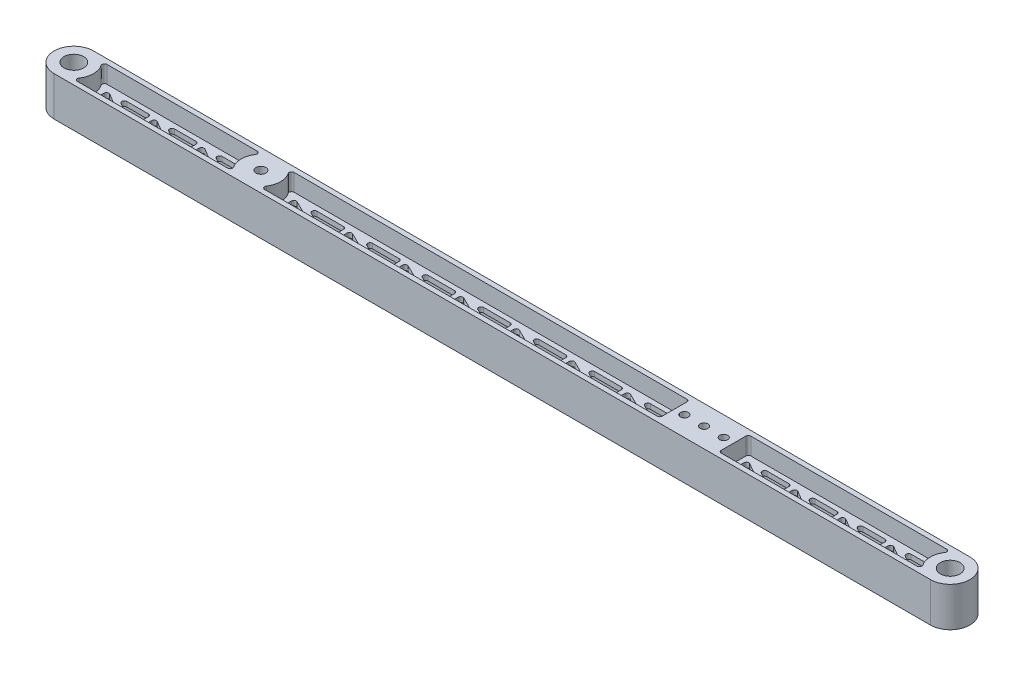
SolidWorks part; units mm, degrees
ref_plane "Front Plane" through (0, 0, 0) normal (0, 0, 1) x (1, 0, 0)
ref_plane "Top Plane" through (0, 0, 0) normal (0, 1, 0) x (1, 0, 0)
ref_plane "Right Plane" through (0, 0, 0) normal (1, 0, 0) x (0, 0, -1)
sketch "Sketch2" plane through (0, 0, 0) normal (0, 1, 0) x (1, 0, 0)
  line L0 (0, 0) -> (120.65, 0)
  line L1 (0, 0) -> (565.15, 0)
  line L2 (0, 0) -> (0, 25.4) construction
  line L3 (0, 25.4) -> (565.15, 25.4)
  line L4 (565.15, 0) -> (565.15, 25.4) construction
  line L5 (120.65, 0) -> (120.65, 25.4) construction
  circle A0 centre (120.65, 12.7) radius 12.7
  arc A1 (565.15, 25.4) -> (565.15, 0) centre (565.15, 12.7) cw
  circle A2 centre (120.65, 12.7) radius 3.175
  circle A3 centre (565.15, 12.7) radius 6.35
  arc A4 (0, 25.4) -> (0, 0) centre (0, 12.7) ccw
  circle A5 centre (0, 12.7) radius 6.35
  dimension "D4" = 6.35
  dimension "D5" = 12.7
  dimension "D6" = 12.7
  dimension "D1" = 565.15
  dimension "D2" = 25.4
  dimension "D3" = 120.65
extrude "Boss-Extrude1" add sketch "Sketch2" along normal blind 25.4 contours A0 L3 L2 L0 | A0 A2 | A1 L3 A0 L1 A3 region at (52.5215, 0, -12.7) region at (350.4658, 0, -12.7) region at (108.3092, 0, -12.7)
sketch "Sketch12" plane through (0, 0, -25.4) normal (0, 0, -1) x (-1, 0, 0)
  line L0 (-565.15, 25.4) -> (-425.45, 25.4)
  line L1 (0, 25.4) -> (-565.15, 25.4) construction
  line L2 (-387.35, 0) -> (-425.45, 0)
  line L3 (-425.45, 25.4) -> (-425.45, 0)
  line L5 (-387.35, 0) -> (-387.35, 25.4)
  line L6 (-425.45, 25.4) -> (-387.35, 25.4)
  line L7 (0, 0) -> (-565.15, 0) construction
  dimension "D1" = 139.7
  dimension "D2" = 38.1
sketch "Sketch13" plane through (0, 25.4, 0) normal (0, 1, 0) x (1, 0, 0)
  line L0 (565.15, 25.4) -> (565.15, 0) construction
  line L1 (0, 25.4) -> (0, 0) construction
  line L2 (565.15, 25.4) -> (565.15, 0) construction
  line L3 (565.15, 22.225) -> (0, 22.225)
  line L4 (0, 3.175) -> (565.15, 3.175)
  line L5 (565.15, 25.4) -> (425.45, 25.4) construction
  line L6 (0, 0) -> (565.15, 0) construction
  line L7 (12.7, 12.7) -> (15.875, 12.7) construction
  line L8 (15.875, 19.05) -> (15.875, 6.35)
  line L9 (15.875, 6.35) -> (37.189, 6.35)
  line L10 (37.189, 6.35) -> (15.875, 19.05)
  line L11 (22.0777, 19.05) -> (43.3917, 6.35)
  line L12 (43.3917, 6.35) -> (43.3917, 19.05)
  line L13 (43.3917, 19.05) -> (22.0777, 19.05)
  line L14 (46.5667, 19.05) -> (46.5667, 6.35)
  line L15 (46.5667, 6.35) -> (67.8806, 6.35)
  line L16 (67.8806, 6.35) -> (46.5667, 19.05)
  line L17 (52.7694, 19.05) -> (74.0833, 6.35)
  line L18 (74.0833, 6.35) -> (74.0833, 19.05)
  line L19 (74.0833, 19.05) -> (52.7694, 19.05)
  line L20 (43.3917, 12.7) -> (46.5667, 12.7) construction
  line L21 (77.2583, 19.05) -> (77.2583, 6.35)
  line L22 (77.2583, 6.35) -> (98.5723, 6.35)
  line L23 (98.5723, 6.35) -> (77.2583, 19.05)
  line L24 (83.461, 19.05) -> (104.775, 6.35)
  line L25 (104.775, 6.35) -> (104.775, 19.05)
  line L26 (104.775, 19.05) -> (83.461, 19.05)
  line L27 (74.0833, 12.7) -> (77.2583, 12.7) construction
  line L28 (107.95, 12.7) -> (104.775, 12.7) construction
  line L29 (133.35, 12.7) -> (136.525, 12.7) construction
  line L30 (136.525, 19.05) -> (136.525, 6.35)
  line L31 (136.525, 6.35) -> (162.0538, 6.35)
  line L32 (162.0538, 6.35) -> (136.525, 19.05)
  line L33 (143.6533, 19.05) -> (169.1821, 6.35)
  line L34 (169.1821, 6.35) -> (169.1821, 19.05)
  line L35 (169.1821, 19.05) -> (143.6533, 19.05)
  line L36 (387.35, 25.4) -> (387.35, 0)
  line L37 (425.45, 25.4) -> (387.35, 25.4) construction
  line L38 (387.35, 0) -> (425.45, 0)
  line L39 (425.45, 0) -> (425.45, 25.4)
  line L40 (387.35, 25.4) -> (425.45, 25.4) construction
  line L41 (425.45, 25.4) -> (387.35, 25.4)
  line L42 (172.3571, 19.05) -> (172.3571, 6.35)
  line L43 (172.3571, 6.35) -> (197.886, 6.35)
  line L44 (197.886, 6.35) -> (172.3571, 19.05)
  line L45 (179.4855, 19.05) -> (205.0143, 6.35)
  line L46 (205.0143, 6.35) -> (205.0143, 19.05)
  line L47 (205.0143, 19.05) -> (179.4855, 19.05)
  line L48 (169.1821, 12.7) -> (172.3571, 12.7) construction
  line L49 (208.1893, 19.05) -> (208.1893, 6.35)
  line L50 (208.1893, 6.35) -> (233.7181, 6.35)
  line L51 (233.7181, 6.35) -> (208.1893, 19.05)
  line L52 (215.3176, 19.05) -> (240.8464, 6.35)
  line L53 (240.8464, 6.35) -> (240.8464, 19.05)
  line L54 (240.8464, 19.05) -> (215.3176, 19.05)
  line L55 (205.0143, 12.7) -> (208.1893, 12.7) construction
  line L56 (244.0214, 19.05) -> (244.0214, 6.35)
  line L57 (244.0214, 6.35) -> (269.5502, 6.35)
  line L58 (269.5502, 6.35) -> (244.0214, 19.05)
  line L59 (251.1498, 19.05) -> (276.6786, 6.35)
  line L60 (276.6786, 6.35) -> (276.6786, 19.05)
  line L61 (276.6786, 19.05) -> (251.1498, 19.05)
  line L62 (240.8464, 12.7) -> (244.0214, 12.7) construction
  line L63 (279.8536, 19.05) -> (279.8536, 6.35)
  line L64 (279.8536, 6.35) -> (305.3824, 6.35)
  line L65 (305.3824, 6.35) -> (279.8536, 19.05)
  line L66 (286.9819, 19.05) -> (312.5107, 6.35)
  line L67 (312.5107, 6.35) -> (312.5107, 19.05)
  line L68 (312.5107, 19.05) -> (286.9819, 19.05)
  line L69 (276.6786, 12.7) -> (279.8536, 12.7) construction
  line L70 (315.6857, 19.05) -> (315.6857, 6.35)
  line L71 (315.6857, 6.35) -> (341.2145, 6.35)
  line L72 (341.2145, 6.35) -> (315.6857, 19.05)
  line L73 (322.814, 19.05) -> (348.3429, 6.35)
  line L74 (348.3429, 6.35) -> (348.3429, 19.05)
  line L75 (348.3429, 19.05) -> (322.814, 19.05)
  line L76 (312.5107, 12.7) -> (315.6857, 12.7) construction
  line L77 (351.5179, 19.05) -> (351.5179, 6.35)
  line L78 (351.5179, 6.35) -> (377.0467, 6.35)
  line L79 (377.0467, 6.35) -> (351.5179, 19.05)
  line L80 (358.6462, 19.05) -> (384.175, 6.35)
  line L81 (384.175, 6.35) -> (384.175, 19.05)
  line L82 (384.175, 19.05) -> (358.6462, 19.05)
  line L83 (348.3429, 12.7) -> (351.5179, 12.7) construction
  line L84 (425.45, 12.7) -> (428.625, 12.7) construction
  line L85 (428.625, 19.05) -> (428.625, 6.35)
  line L86 (428.625, 6.35) -> (450.1567, 6.35)
  line L87 (450.1567, 6.35) -> (428.625, 19.05)
  line L88 (434.8745, 19.05) -> (456.4062, 6.35)
  line L89 (456.4062, 6.35) -> (456.4062, 19.05)
  line L90 (456.4062, 19.05) -> (434.8745, 19.05)
  line L91 (459.5812, 19.05) -> (459.5812, 6.35)
  line L92 (459.5812, 6.35) -> (481.113, 6.35)
  line L93 (481.113, 6.35) -> (459.5812, 19.05)
  line L94 (465.8308, 19.05) -> (487.3625, 6.35)
  line L95 (487.3625, 6.35) -> (487.3625, 19.05)
  line L96 (487.3625, 19.05) -> (465.8308, 19.05)
  line L97 (456.4062, 12.7) -> (459.5812, 12.7) construction
  line L98 (490.5375, 19.05) -> (490.5375, 6.35)
  line L99 (490.5375, 6.35) -> (512.0692, 6.35)
  line L100 (512.0692, 6.35) -> (490.5375, 19.05)
  line L101 (496.787, 19.05) -> (518.3187, 6.35)
  line L102 (518.3187, 6.35) -> (518.3187, 19.05)
  line L103 (518.3187, 19.05) -> (496.787, 19.05)
  line L104 (487.3625, 12.7) -> (490.5375, 12.7) construction
  line L105 (521.4937, 19.05) -> (521.4937, 6.35)
  line L106 (521.4937, 6.35) -> (543.0255, 6.35)
  line L107 (543.0255, 6.35) -> (521.4937, 19.05)
  line L108 (527.7433, 19.05) -> (549.275, 6.35)
  line L109 (549.275, 6.35) -> (549.275, 19.05)
  line L110 (549.275, 19.05) -> (527.7433, 19.05)
  line L111 (518.3187, 12.7) -> (521.4937, 12.7) construction
  line L112 (387.35, 12.7) -> (425.45, 12.7) construction
  line L113 (565.15, 12.7) -> (552.45, 12.7) construction
  line L114 (552.45, 12.7) -> (552.45, 25.4) construction
  line L115 (552.45, 25.4) -> (552.45, 3.175) construction
  line L116 (393.7, 25.4) -> (393.7, 0) construction
  line L117 (406.4, 25.4) -> (406.4, 0) construction
  line L118 (406.4, 25.4) -> (406.4, 0) construction
  line L119 (419.1, 0) -> (419.1, 25.4) construction
  circle A0 centre (565.15, 12.7) radius 12.7
  circle A1 centre (120.65, 12.7) radius 12.7
  circle A2 centre (0, 12.7) radius 12.7
  circle A3 centre (393.7, 12.7) radius 6.35
  circle A4 centre (419.1, 12.7) radius 6.35
  circle A5 centre (406.4, 12.7) radius 6.35
  dimension "D1" = 25.4
  dimension "D9" = 3.175
  dimension "D30" = 12.7
  dimension "D31" = 12.7
  dimension "D32" = 12.7
  dimension "D2" = 3.175
  dimension "D3" = 3.175
  dimension "D4" = 3.175
  dimension "D5" = 3.175
  dimension "D6" = 3.175
  dimension "D7" = 3.175
  dimension "D10" = 3.175
  dimension "D11" = 3.175
  dimension "D12" = 3.175
  dimension "D13" = 3.175
  dimension "D14" = 3.175
  dimension "D15" = 139.7
  dimension "D16" = 38.1
  dimension "D17" = 7
  dimension "D18" = 3.175
  dimension "D19" = 3.175
  dimension "D20" = 3.175
  dimension "D21" = 3.175
  dimension "D22" = 3.175
  dimension "D23" = 3.175
  dimension "D25" = 3.175
  dimension "D26" = 3.175
  dimension "D27" = 6.35
  dimension "D28" = 12.7
  dimension "D29" = 6.35
  dimension "D8" = 3
  dimension "D24" = 4
extrude "Cut-Extrude2" cut sketch "Sketch13" against normal through all contours L109 L110 L108 | L106 L107 L105 | L102 L103 L101 | L99 L100 L98 | L92 L93 L91 | L89 L90 L88 | L86 L87 L85 | L78 L79 L77 | L81 L82 L80 | L74 L75 L73 | L71 L72 L70 | L67 L68 L66 | L64 L65 L63 | L60 L61 L59 | L57 L58 L56 | L53 L54 L52 | L50 L51 L49 | L46 L47 L45 | L43 L44 L42 | L34 L35 L33 | L31 L32 L30 | L25 L26 L24 | L22 L23 L21 | L18 L19 L17 | L15 L16 L14 | L12 L13 L11 | L9 L10 L8 | L96 L94 L95 region at (22.9797, 25.4, -10.5833) region at (36.287, 25.4, -14.8167) region at (53.6713, 25.4, -10.5833) region at (66.9787, 25.4, -14.8167) region at (84.363, 25.4, -10.5833) region at (97.6703, 25.4, -14.8167) region at (145.0346, 25.4, -10.5833) region at (160.6725, 25.4, -14.8167) region at (180.8667, 25.4, -10.5833) region at (196.5047, 25.4, -14.8167) region at (216.6989, 25.4, -10.5833) region at (232.3368, 25.4, -14.8167) region at (252.531, 25.4, -10.5833) region at (268.169, 25.4, -14.8167) region at (288.3632, 25.4, -10.5833) region at (304.0011, 25.4, -14.8167) region at (324.1953, 25.4, -10.5833) region at (339.8333, 25.4, -14.8167) region at (360.0275, 25.4, -10.5833) region at (375.6654, 25.4, -14.8167) region at (435.8022, 25.4, -10.5833) region at (449.229, 25.4, -14.8167) region at (466.7585, 25.4, -10.5833) region at (497.7147, 25.4, -10.5833) region at (511.1415, 25.4, -14.8167) region at (528.671, 25.4, -10.5833) region at (542.0978, 25.4, -14.8167)
extrude "Cut-Extrude3" cut sketch "Sketch13<4>" against normal blind 11.1125 contours A2 L4 A1 L3 L10 L9 L8 L13 L12 L11 L16 L15 L14 L19 L18 L17 L23 L22 L21 L26 L25 L24 | A1 L4 L36 L3 L32 L31 L30 L35 L34 L33 L44 L43 L42 L47 L46 L45 L51 L50 L49 L54 L53 L52 L58 L57 L56 L61 L60 L59 L65 L64 L63 L68 L67 L66 L72 L71 L70 L75 L74 | A0 L3 L39 L4 L87 L86 L85 L90 L89 L88 L93 L92 L91 L96 L95 L94 L100 L99 L98 L103 L102 L101 L107 L106 L105 L110 L109 L108 region at (490.155, 25.4, -12.7) region at (259.1074, 25.4, -12.7) region at (60.325, 25.4, -12.7)
sketch "Sketch13<4>" plane through (0, 25.4, 0) normal (0, 1, 0) x (1, 0, 0) same geometry as "Sketch13"
ref_plane "Plane1" through (0, 12.7, 0) normal (0, -1, 0) x (-1, 0, 0)
mirror "Mirror1" about plane through (0, 12.7, 0) normal (0, -1, 0) of "Cut-Extrude3"
fillet "Fillet1" radius 1.5875 108 edges at (104.775, 12.7, -19.05) (83.461, 12.7, -19.05) (98.5723, 12.7, -6.35) (77.2583, 12.7, -6.35) (77.2583, 12.7, -19.05) (74.0833, 12.7, -19.05) (74.0833, 12.7, -6.35) (52.7694, 12.7, -19.05) (67.8806, 12.7, -6.35) (46.5667, 12.7, -6.35) (46.5667, 12.7, -19.05) (43.3917, 12.7, -19.05) (43.3917, 12.7, -6.35) (22.0777, 12.7, -19.05) (37.189, 12.7, -6.35) (15.875, 12.7, -6.35) (15.875, 12.7, -19.05) (104.775, 12.7, -6.35) (384.175, 12.7, -19.05) (358.6462, 12.7, -19.05) (377.0467, 12.7, -6.35) (351.5179, 12.7, -6.35) (351.5179, 12.7, -19.05) (348.3429, 12.7, -19.05) (348.3429, 12.7, -6.35) (322.814, 12.7, -19.05) (341.2145, 12.7, -6.35) (315.6857, 12.7, -6.35) (315.6857, 12.7, -19.05) (312.5107, 12.7, -19.05) (312.5107, 12.7, -6.35) (286.9819, 12.7, -19.05) (305.3824, 12.7, -6.35) (279.8536, 12.7, -6.35) (279.8536, 12.7, -19.05) (276.6786, 12.7, -19.05) (276.6786, 12.7, -6.35) (251.1498, 12.7, -19.05) (269.5502, 12.7, -6.35) (244.0214, 12.7, -6.35) (244.0214, 12.7, -19.05) (240.8464, 12.7, -19.05) (240.8464, 12.7, -6.35) (215.3176, 12.7, -19.05) (233.7181, 12.7, -6.35) (208.1893, 12.7, -6.35) (208.1893, 12.7, -19.05) (205.0143, 12.7, -19.05) (205.0143, 12.7, -6.35) (179.4855, 12.7, -19.05) (197.886, 12.7, -6.35) (172.3571, 12.7, -6.35) (172.3571, 12.7, -19.05) (169.1821, 12.7, -19.05) (169.1821, 12.7, -6.35) (143.6533, 12.7, -19.05) (162.0538, 12.7, -6.35) (136.525, 12.7, -6.35) (136.525, 12.7, -19.05) (384.175, 12.7, -6.35) (112.2497, 5.5562, -22.225) (112.2497, 5.5562, -3.175) (8.4003, 5.5562, -3.175) (8.4003, 5.5562, -22.225) (387.35, 5.5562, -22.225) (129.0503, 5.5562, -3.175) (129.0503, 5.5562, -22.225) (387.35, 5.5562, -3.175) (425.45, 19.8438, -22.225) (425.45, 19.8438, -3.175) (556.7497, 19.8438, -3.175) (112.2497, 19.8438, -3.175) (112.2497, 19.8438, -22.225) (8.4003, 19.8438, -22.225) (8.4003, 19.8438, -3.175) (387.35, 19.8438, -3.175) (387.35, 19.8438, -22.225) (129.0503, 19.8438, -22.225) (129.0503, 19.8438, -3.175) (556.7497, 19.8438, -22.225) (549.275, 12.7, -6.35) (527.7433, 12.7, -19.05) (543.0255, 12.7, -6.35) (521.4937, 12.7, -6.35) (521.4937, 12.7, -19.05) (518.3187, 12.7, -19.05) (518.3187, 12.7, -6.35) (496.787, 12.7, -19.05) (512.0692, 12.7, -6.35) (490.5375, 12.7, -6.35) (490.5375, 12.7, -19.05) (487.3625, 12.7, -19.05) (487.3625, 12.7, -6.35) (465.8308, 12.7, -19.05) (481.113, 12.7, -6.35) (459.5812, 12.7, -6.35) (459.5812, 12.7, -19.05) (456.4062, 12.7, -19.05) (456.4062, 12.7, -6.35) (434.8745, 12.7, -19.05) (450.1567, 12.7, -6.35) (428.625, 12.7, -6.35) (428.625, 12.7, -19.05) (549.275, 12.7, -19.05) (556.7497, 5.5562, -22.225) (425.45, 5.5562, -22.225) (425.45, 5.5562, -3.175) (556.7497, 5.5562, -3.175)
hole_wizard "1/4-20 Tapped Hole1" positions "3DSketch1" profile "Sketch14" tap size "1/4-20" standard "ANSI Inch"
sketch3d "3DSketch1"
  point P0 (393.7, 25.4, -12.7)
  point P3 (406.4, 25.4, -12.7)
  point P6 (419.1, 25.4, -12.7)
sketch "Sketch14" plane through (393.7, 25.4, -12.7) normal (1, 0, 0) x (0, 0, 1)
  line L0 (0, 0) -> (0, 20.5838)
  line L1 (0, 20.5838) -> (2.5527, 19.05)
  line L2 (2.5527, 19.05) -> (2.5527, 0)
  line L5 (2.5527, 0) -> (0, 0)
  line L10 (0, 20.5838) -> (-2.5527, 19.05) construction
  line L11 (0, -6.35) -> (0, 107.95) construction
  dimension "Tap Drill Dia." = 5.1054
  dimension "Tap Drill Depth" = 19.05
  dimension "Drill Angle" = 118
cosmetic thread "Hole Thread1" parameters "D1"=12.7, "D2"=6.35
cosmetic thread "Hole Thread2" parameters "D1"=12.7, "D2"=6.35
cosmetic thread "Hole Thread3" parameters "D1"=12.7, "D2"=6.35
